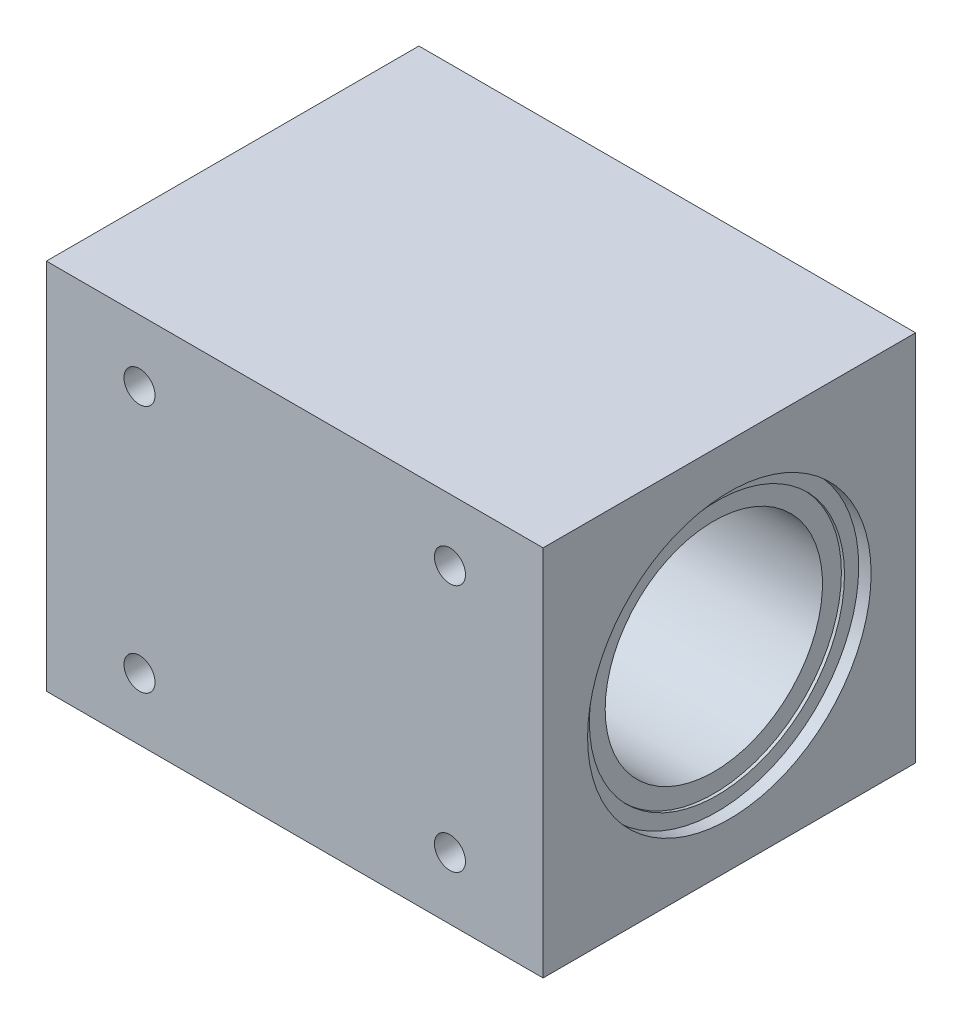
SolidWorks part; units mm, degrees
ref_plane "前视基准面" through (0, 0, 0) normal (0, 0, 1) x (1, 0, 0)
ref_plane "上视基准面" through (0, 0, 0) normal (0, 1, 0) x (1, 0, 0)
ref_plane "右视基准面" through (0, 0, 0) normal (1, 0, 0) x (0, 0, -1)
sketch "草图1" plane through (0, 0, 0) normal (1, 0, 0) x (0, 0, -1)
  line L0 (-30, -30) -> (30, -30)
  line L1 (30, -30) -> (30, 30)
  line L2 (30, 30) -> (-30, 30)
  line L3 (-30, 30) -> (-30, -30)
  circle A0 centre (0, 0) radius 17.5
extrude "凸台-拉伸1" add sketch "草图1" along normal blind 80
ref_plane "基准面1" through (40, 0, 0) normal (1, 0, 0) x (0, 0, -1)
ref_plane "基准面2" through (65, 0, 0) normal (1, 0, 0) x (0, 0, -1)
ref_plane "基准面4" through (5, 0, 0) normal (1, 0, 0) x (0, 0, -1)
sketch "草图6" plane through (0, 0, 0) normal (0, 0, 1) x (1, 0, 0)
  line L0 (0, 17.5) -> (2.5, 17.5)
  line L1 (2.5, 17.5) -> (2.5, 20.5476)
  line L2 (2.5, 20.5476) -> (2, 20.5476)
  line L3 (2, 20.5476) -> (2, 22.8333)
  line L4 (2, 22.8333) -> (0, 22.8333)
  line L5 (0, 22.8333) -> (0, 17.5)
  line L6 (80, 0) -> (0, 0) construction
revolve "切除-旋转5" cut sketch "草图6" angle 360 about L6 reverse direction yes
sketch "草图7" plane through (0, 0, 0) normal (0, 0, 1) x (1, 0, 0)
  line L0 (77.5, 17.5) -> (80, 17.5)
  line L1 (80, 17.5) -> (80, 22.8333)
  line L2 (80, 22.8333) -> (78, 22.8333)
  line L3 (78, 22.8333) -> (78, 20.5476)
  line L4 (78, 20.5476) -> (77.5, 20.5476)
  line L5 (77.5, 20.5476) -> (77.5, 17.5)
  line L6 (80, 0) -> (0, 0) construction
revolve "切除-旋转6" cut sketch "草图7" angle 360 about L6 reverse direction yes
ref_plane "For barrel XY" through (0, 0, 0) normal (-1, 0, 0) x (0, 0, 1)
ref_plane "For barrel XZ" through (0, 0, 0) normal (0, 1, 0) x (1, 0, 0)
ref_plane "For barrel YZ" through (0, 0, 0) normal (0, 0, -1) x (-1, 0, 0)
ref_axis "For barrel X" through (0, 0, 80.9) along (0, 0, -1)
ref_axis "For barrel Y" through (0, 50, 0) along (0, -1, 0)
ref_axis "For barrel Z" through (-80.9, 0, 0) along (1, 0, 0)
sketch3d "For barrel"
  point P0 (0, 0, 0)
ref_plane "For piston XY" through (5, 0, 0) normal (1, 0, 0) x (0, 0, -1)
ref_plane "For piston XZ" through (0, 0, 0) normal (0, -1, 0) x (-1, 0, 0)
ref_plane "For piston YZ" through (0, 0, 0) normal (0, 0, -1) x (-1, 0, 0)
ref_axis "For piston X" through (5, 0, 80.9) along (0, 0, -1)
ref_axis "For piston Y" through (5, -50, 0) along (0, 1, 0)
ref_axis "For piston Z" through (80.9, 0, 0) along (-1, 0, 0)
sketch3d "For piston"
  point P0 (5, 0, 0)
hole_wizard "M6 螺纹孔1" positions "草图9" profile "草图8" tap size "M6" standard "ISO"
sketch "草图9" plane through (0, 0, 30) normal (0, 0, 1) x (1, 0, 0)
  line L0 (0, 0) -> (80, 0) construction
  line L1 (80, 30) -> (80, -30) construction
  line L4 (40, 0) -> (40, 30) construction
  line L5 (80, 30) -> (0, 30) construction
  point P15 (15, 20)
  point P17 (15, -20)
  point P19 (65, -20)
  point P21 (65, 20)
  dimension "D1" = 50
  dimension "D2" = 40
sketch "草图8" plane through (15, 20, 30) normal (1, 0, 0) x (0, -1, 0)
  line L0 (0, 0) -> (0, 18.5022)
  line L1 (0, 18.5022) -> (2.5, 17)
  line L2 (2.5, 17) -> (2.5, 0)
  line L5 (2.5, 0) -> (0, 0)
  line L10 (0, 18.5022) -> (-2.5, 17) construction
  line L11 (0, -6.35) -> (0, 107.95) construction
  dimension "螺纹孔钻头直径" = 5
  dimension "螺纹孔钻头深度" = 17
  dimension "导头角度" = 118
cosmetic thread "孔螺蚊线1" parameters "D1"=12, "D2"=6
cosmetic thread "孔螺蚊线2" parameters "D1"=12, "D2"=6
cosmetic thread "孔螺蚊线3" parameters "D1"=12, "D2"=6
cosmetic thread "孔螺蚊线4" parameters "D1"=12, "D2"=6
